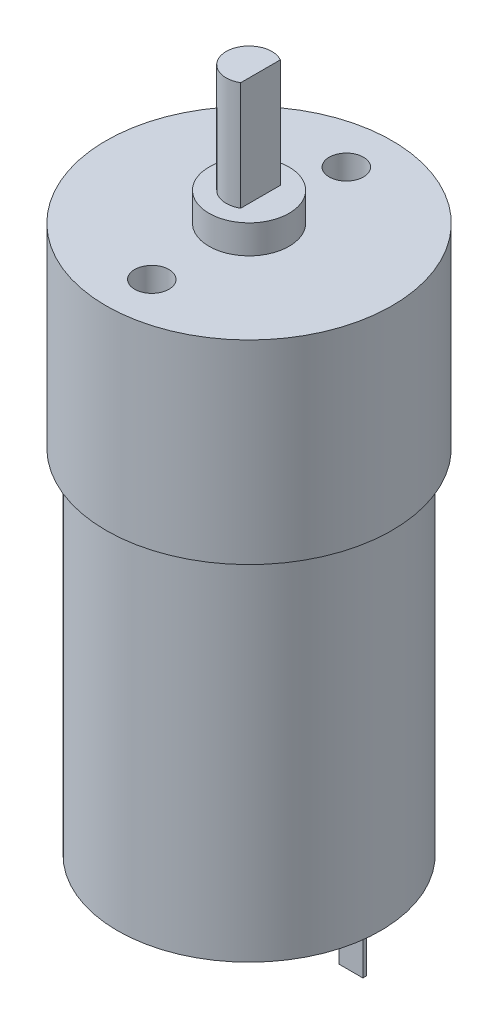
SolidWorks part; units mm, degrees
ref_plane "Front Plane" through (0, 0, 0) normal (0, 0, 1) x (1, 0, 0)
ref_plane "Top Plane" through (0, 0, 0) normal (0, 1, 0) x (1, 0, 0)
ref_plane "Right Plane" through (0, 0, 0) normal (1, 0, 0) x (0, 0, -1)
sketch "Sketch2" plane through (0, 0, 0) normal (0, 1, 0) x (1, 0, 0)
  circle A0 centre (0, 0) radius 12.5
  circle A1 centre (0, 0) radius 2
  circle A2 centre (0, 0) radius 3.5
  dimension "D1" = 25
  dimension "D2" = 4
  dimension "D3" = 7
extrude "Boss-Extrude1" add sketch "Sketch2" against normal blind 17 contours A1 | A0 A1 | A2 A1 region at (-12.1464, 0, 0) region at (0, 0, 0) region at (-3.401, 0, 0)
extrude "Boss-Extrude2" add sketch "Sketch2<3>" along normal blind 12 contours A1 region at (0, 0, 0)
sketch "Sketch2<3>" plane through (0, 0, 0) normal (0, 1, 0) x (1, 0, 0) same geometry as "Sketch2"
extrude "Boss-Extrude3" add sketch "Sketch2<4>" along normal blind 2.5 contours A2 A1 region at (-3.401, 0, 0)
sketch "Sketch2<4>" plane through (0, 0, 0) normal (0, 1, 0) x (1, 0, 0) same geometry as "Sketch2"
sketch "Sketch4" plane through (0, -17, 0) normal (0, -1, 0) x (1, 0, 0)
  circle A0 centre (0, 0) radius 11.5
  circle A1 centre (0, 0) radius 12.5 construction
  dimension "D1" = 1
extrude "Boss-Extrude4" add sketch "Sketch4" along normal blind 30.8
sketch "Sketch5" plane through (0, -47.8, 0) normal (0, -1, 0) x (1, 0, 0)
  line L0 (0, -11.5) -> (0, 11.5) construction
  line L1 (-10.1, -0.15) -> (-8, -0.15)
  line L2 (-10.1, -0.15) -> (-10.1, 0.15)
  line L3 (-10.1, 0.15) -> (-8, 0.15)
  line L4 (-8, -0.15) -> (-8, 0.15)
  line L5 (-10.1, -0.15) -> (-8, 0.15) construction
  line L6 (-10.1, 0.15) -> (-8, -0.15) construction
  line L11 (10.1, 0.15) -> (8, -0.15) construction
  line L12 (10.1, -0.15) -> (8, 0.15) construction
  line L13 (8, -0.15) -> (8, 0.15)
  line L14 (10.1, 0.15) -> (8, 0.15)
  line L15 (10.1, -0.15) -> (10.1, 0.15)
  line L16 (10.1, -0.15) -> (8, -0.15)
  circle A0 centre (0, 0) radius 11.5 construction
  point P0 (-9.05, 0)
  point P13 (0, 0)
  point P16 (9.05, 0)
  dimension "D1" = 2.1
  dimension "D2" = 0.3
  dimension "D3" = 9.05
extrude "Boss-Extrude5" add sketch "Sketch5" along normal blind 4.2
sketch "Sketch6" plane through (0, 0, 0) normal (0, 1, 0) x (1, 0, 0)
  line L0 (-12.5, 0) -> (12.5, 0) construction
  circle A0 centre (0, -8.5) radius 1.5
  circle A1 centre (0, 0) radius 12.5 construction
  circle A2 centre (0, 8.5) radius 1.5
  point P12 (0, 0)
  dimension "D1" = 3
  dimension "D2" = 8.5
extrude "Cut-Extrude1" cut sketch "Sketch6" against normal blind 5
sketch "Sketch7" plane through (0, 12, 0) normal (0, 1, 0) x (1, 0, 0)
  line L0 (1, -1.7321) -> (1, 1.7321)
  line L1 (2, 0) -> (-2, 0) construction
  circle A0 centre (0, 0) radius 2 construction
  circle A1 centre (0, 0) radius 2 construction
  circle A2 centre (0, 0) radius 2
  point P11 (0, 0)
  circle M2 centre (0, 0) radius 2
  dimension "D1" = 3
extrude "Cut-Extrude2" cut sketch "Sketch7" against normal up to surface (9.5 mm away) contours L1 L0 M2 | L1 A2 L0 region at (1.41, 12, 0.6784) region at (1.41, 12, -0.6784) up to face at (0, 2.5, 2)
